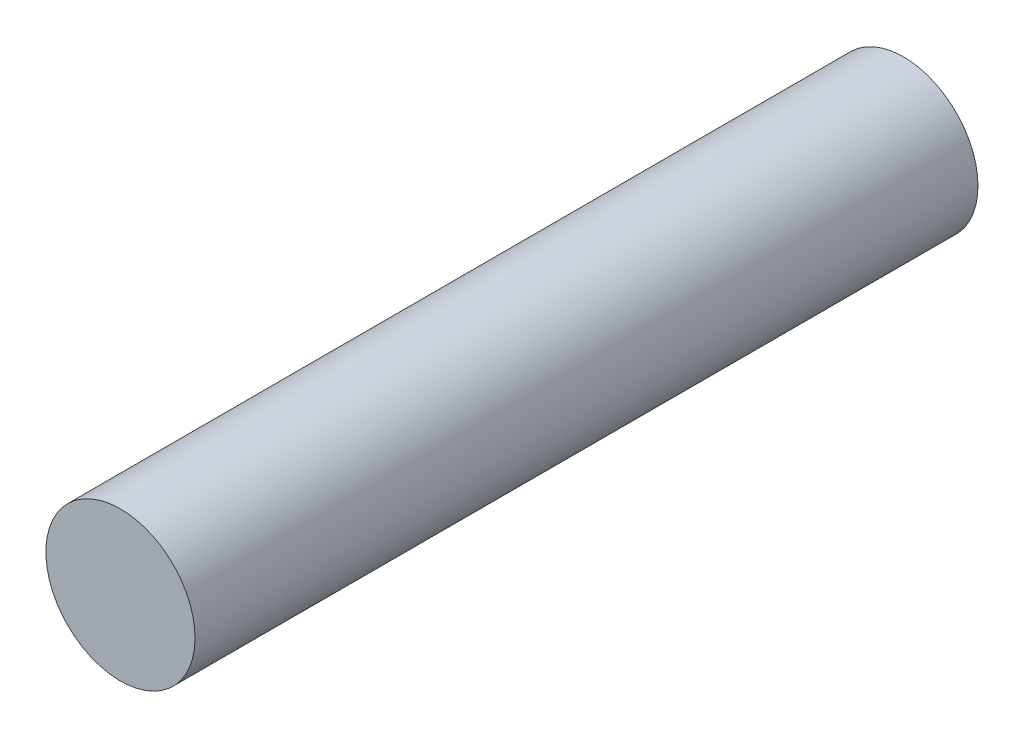
SolidWorks part; units mm, degrees
ref_plane "Front Plane" through (0, 0, 0) normal (0, 0, 1) x (1, 0, 0)
ref_plane "Top Plane" through (0, 0, 0) normal (0, 1, 0) x (1, 0, 0)
ref_plane "Right Plane" through (0, 0, 0) normal (1, 0, 0) x (0, 0, -1)
sketch "Sketch1" plane through (0, 0, 0) normal (0, 0, 1) x (1, 0, 0)
  circle A0 centre (0, 0) radius 4.7625
  dimension "D1" = 9.525
extrude "Boss-Extrude1" add sketch "Sketch1" along normal blind 50
ref_axis "Axis1" through (0, 0, 50) along (0, 0, -1)
